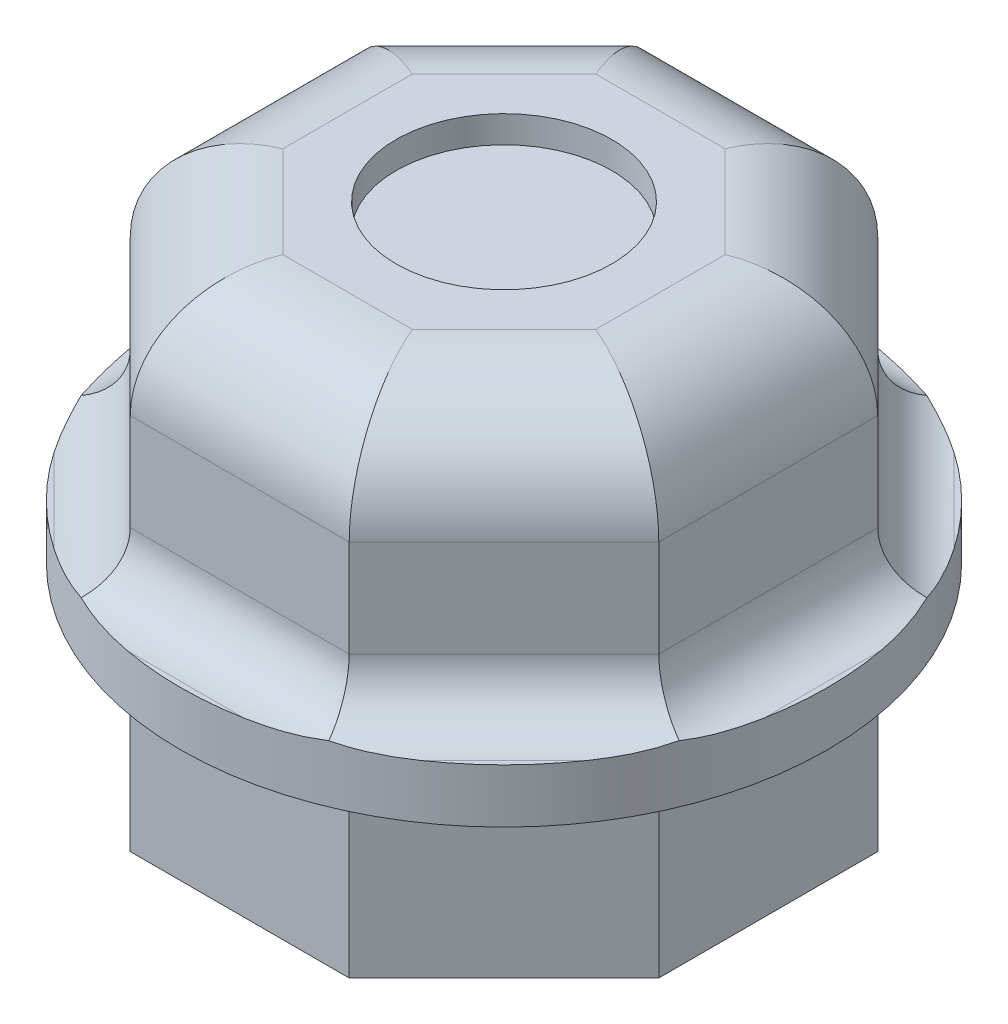
SolidWorks part; units mm, degrees
ref_plane "Front Plane" through (0, 0, 0) normal (0, 0, 1) x (1, 0, 0)
ref_plane "Top Plane" through (0, 0, 0) normal (0, 1, 0) x (1, 0, 0)
ref_plane "Right Plane" through (0, 0, 0) normal (1, 0, 0) x (0, 0, -1)
sketch "Sketch1" plane through (0, 0, 0) normal (0, 1, 0) x (1, 0, 0)
  line L1 (2.0296, 4.9) -> (-2.0296, 4.9)
  line L2 (-2.0296, 4.9) -> (-4.9, 2.0296)
  line L3 (-4.9, 2.0296) -> (-4.9, -2.0296)
  line L4 (-4.9, -2.0296) -> (-2.0296, -4.9)
  line L5 (-2.0296, -4.9) -> (2.0296, -4.9)
  line L6 (2.0296, -4.9) -> (4.9, -2.0296)
  line L7 (4.9, -2.0296) -> (4.9, 2.0296)
  line L8 (4.9, 2.0296) -> (2.0296, 4.9)
  circle A0 centre (0, 0) radius 4.9 construction
  circle A1 centre (0, 0) radius 4.9 construction
  dimension "D1" = 9.8
extrude "Boss-Extrude1" add sketch "Sketch1" along normal blind 9
sketch "Sketch2" plane through (0, 9, 0) normal (0, 1, 0) x (1, 0, 0)
  circle A0 centre (0, 0) radius 2
  dimension "D1" = 4
extrude "Cut-Extrude1" cut sketch "Sketch2" against normal blind 0.5
sketch "Sketch3" plane through (0, 0, 0) normal (0, -1, 0) x (1, 0, 0)
  circle A0 centre (0, 0) radius 6
  dimension "D1" = 12
extrude "Boss-Extrude2" add sketch "Sketch3" against normal blind 1 from offset 3.2 offset against normal yes
fillet "Fillet1" radius 2 8 edges at (-3.4648, 9, -3.4648) (-4.9, 9, 0) (-3.4648, 9, 3.4648) (0, 9, 4.9) (3.4648, 9, 3.4648) (4.9, 9, 0) (3.4648, 9, -3.4648) (0, 9, -4.9)
fillet "Fillet2" radius 1 8 edges at (-3.4648, 4.2, -3.4648) (-4.9, 4.2, 0) (-3.4648, 4.2, 3.4648) (0, 4.2, 4.9) (4.9, 4.2, 0) (3.4648, 4.2, 3.4648) (3.4648, 4.2, -3.4648) (0, 4.2, -4.9)
